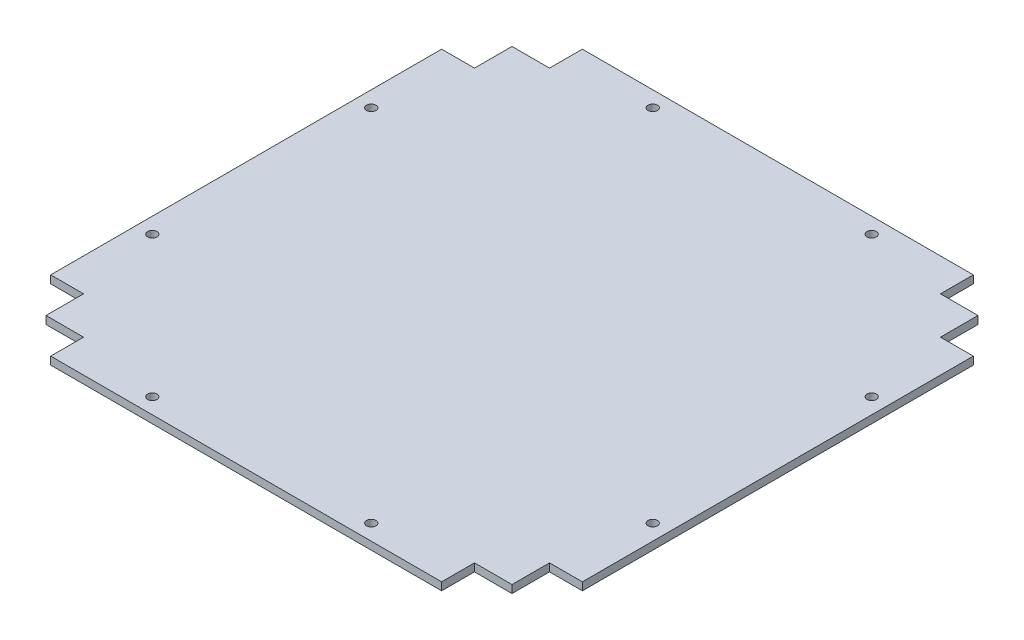
SolidWorks part; units mm, degrees
ref_plane "Front Plane" through (0, 0, 0) normal (0, 0, 1) x (1, 0, 0)
ref_plane "Top Plane" through (0, 0, 0) normal (0, 1, 0) x (1, 0, 0)
ref_plane "Right Plane" through (0, 0, 0) normal (1, 0, 0) x (0, 0, -1)
sketch "Sketch1" plane through (0, 0, 0) normal (0, 1, 0) x (1, 0, 0)
  line L0 (0, -45) -> (21, -45)
  line L1 (45, 0) -> (295, 0)
  line L2 (0, -45) -> (0, -295)
  line L3 (45, -340) -> (295, -340)
  line L4 (340, -45) -> (340, -295)
  line L5 (21, -45) -> (21, -21)
  line L6 (21, -21) -> (45, -21)
  line L7 (45, -21) -> (45, 0)
  line L8 (170, -340) -> (170, -241.5476) construction
  line L9 (340, -170) -> (240.7442, -170) construction
  line L10 (45, -319) -> (45, -340)
  line L11 (21, -319) -> (45, -319)
  line L12 (21, -295) -> (21, -319)
  line L13 (0, -295) -> (21, -295)
  line L14 (295, -21) -> (295, 0)
  line L15 (319, -21) -> (295, -21)
  line L16 (319, -45) -> (319, -21)
  line L17 (340, -45) -> (319, -45)
  line L18 (295, -319) -> (295, -340)
  line L19 (319, -319) -> (295, -319)
  line L20 (319, -295) -> (319, -319)
  line L21 (340, -295) -> (319, -295)
  dimension "D1" = 340
  dimension "D2" = 340
  dimension "D3" = 45
  dimension "D4" = 45
  dimension "D5" = 21
  dimension "D6" = 21
  dimension "D7" = 170
extrude "Boss-Extrude1" add sketch "Sketch1" along normal blind 5
sketch "Sketch2" plane through (0, 5, 0) normal (0, 1, 0) x (1, 0, 0)
  line L0 (45, 0) -> (45, -10) construction
  line L1 (45, 0) -> (45, -21) construction
  line L2 (45, -10) -> (295, -10) construction
  line L3 (295, -21) -> (295, 0) construction
  line L4 (0, -170) -> (142.2873, -170) construction
  line L5 (0, -45) -> (0, -295) construction
  line L6 (170, -340) -> (170, -223.8857)
  line L7 (45, -340) -> (295, -340) construction
  line L8 (21, -21) -> (138.7279, -138.7279)
  circle A0 centre (100, -10) radius 3
  circle A1 centre (240, -10) radius 3
  circle A2 centre (240, -330) radius 3
  circle A3 centre (100, -330) radius 3
  circle A4 centre (10, -240) radius 3
  circle A5 centre (10, -100) radius 3
  circle A6 centre (330, -240) radius 3
  circle A7 centre (330, -100) radius 3
  point P12 (170, -10)
  point P36 (0, 0)
  dimension "D2" = 6
  dimension "D3" = 6
  dimension "D1" = 10
  dimension "D4" = 70
  dimension "D5" = 70
extrude "Cut-Extrude1" cut sketch "Sketch2" against normal blind 57 and the other way blind 57 contours A0 | A1 | A6 | A7 | A2 | A3 | A4 | A5
